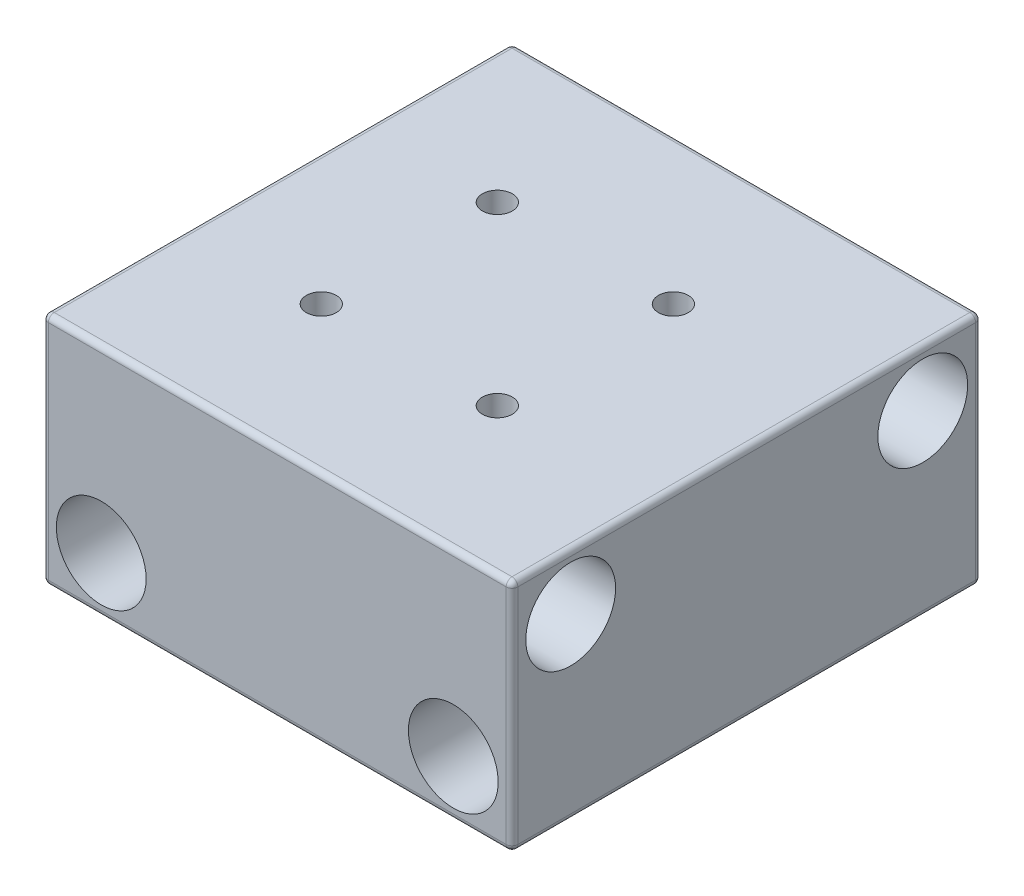
SolidWorks part; units mm, degrees
ref_plane "Front Plane" through (0, 0, 0) normal (0, 0, 1) x (1, 0, 0)
ref_plane "Top Plane" through (0, 0, 0) normal (0, 1, 0) x (1, 0, 0)
ref_plane "Right Plane" through (0, 0, 0) normal (1, 0, 0) x (0, 0, -1)
sketch "Sketch1" plane through (0, 0, 0) normal (0, 1, 0) x (1, 0, 0)
  line L1 (40, -40) -> (-40, -40)
  line L2 (40, -40) -> (40, 40)
  line L3 (40, 40) -> (-40, 40)
  line L4 (-40, -40) -> (-40, 40)
  line L5 (40, -40) -> (-40, 40) construction
  line L6 (40, 40) -> (-40, -40) construction
  point P0 (0, 0)
  dimension "D1" = 80
  dimension "D2" = 80
extrude "Boss-Extrude1" add sketch "Sketch1" along normal mid plane 40
sketch "Sketch3" plane through (0, 0, 40) normal (0, 0, 1) x (1, 0, 0)
  line L0 (-40, 20) -> (-40, -20) construction
  line L1 (-40, -20) -> (40, -20) construction
  line L2 (0, -31.3339) -> (0, 31.9178) construction
  circle A0 centre (-30, -10.5) radius 4.5
  circle A1 centre (30, -10.5) radius 4.5
  circle A2 centre (-30, -10.5) radius 7.65
  circle A3 centre (30, -10.5) radius 7.65
  dimension "D1" = 10
  dimension "D2" = 9.5
  dimension "D3" = 9
  dimension "D4" = 15.3
extrude "Cut-Extrude2" cut sketch "Sketch3" against normal through all contours A0 | A1
extrude "Cut-Extrude3" cut sketch "Sketch3<4>" against normal blind 24.5
sketch "Sketch3<4>" plane through (0, 0, 40) normal (0, 0, 1) x (1, 0, 0) same geometry as "Sketch3"
mirror "Mirror1" about plane through (0, 0, 0) normal (0, 0, 1) of "Cut-Extrude3"
sketch "Sketch7" plane through (40, 0, 0) normal (1, 0, 0) x (0, 0, -1)
  line L0 (-40, 20) -> (-40, -20) construction
  line L1 (-40, 20) -> (40, 20) construction
  line L2 (0, -31.9835) -> (0, 30.527) construction
  circle A0 centre (-30, 10.5) radius 4.5
  circle A1 centre (30, 10.5) radius 4.5
  circle A2 centre (-30, 10.5) radius 7.65
  circle A3 centre (30, 10.5) radius 7.65
  dimension "D1" = 9
  dimension "D3" = 9.5
  dimension "D4" = 15.3
  dimension "D2" = 10
extrude "Cut-Extrude4" cut sketch "Sketch7" against normal through all contours A0 | A1
extrude "Cut-Extrude5" cut sketch "Sketch7<4>" against normal blind 24.5
sketch "Sketch7<4>" plane through (40, 0, 0) normal (1, 0, 0) x (0, 0, -1) same geometry as "Sketch7"
mirror "Mirror2" about plane through (0, 0, 0) normal (1, 0, 0) of "Cut-Extrude5"
fillet "Fillet1" radius 1 12 edges at (0, -20, 40) (0, 20, 40) (-40, 0, 40) (-40, -20, 0) (-40, 20, 0) (-40, 0, -40) (0, -20, -40) (0, 20, -40) (40, 20, 0) (40, 0, -40) (40, -20, 0) (40, 0, 40)
sketch "Sketch8" plane through (0, 20, 0) normal (0, 1, 0) x (1, 0, 0)
  circle A0 centre (-17.5, 15) radius 2.55
  circle A1 centre (12.5, 15) radius 2.55
  circle A2 centre (12.5, -15) radius 2.55
  circle A3 centre (-17.5, -15) radius 2.55
  point P0 (0, 0)
  point P16 (-2.5, 0)
  dimension "D3" = 5.1
  dimension "D1" = 30
  dimension "30" = 30
  dimension "D4" = 4
extrude "Cut-Extrude7" cut sketch "Sketch8" against normal through all contours A0 | A1 | A2 | A3
